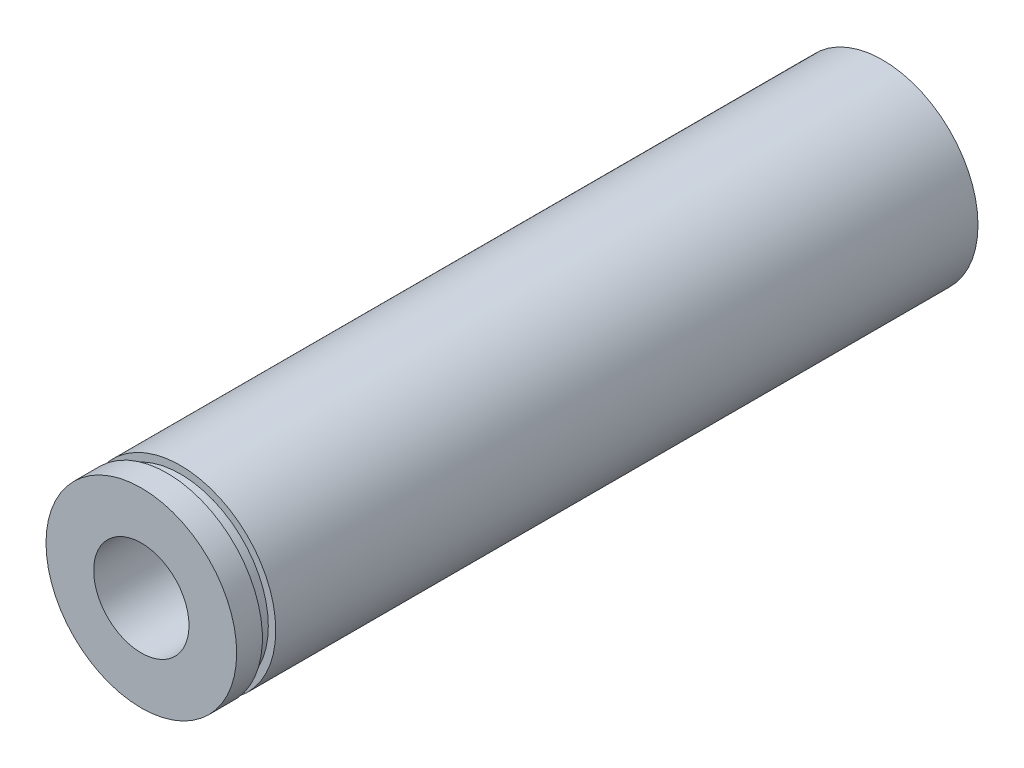
SolidWorks part; units mm, degrees
ref_plane "Front Plane" through (0, 0, 0) normal (0, 0, 1) x (1, 0, 0)
ref_plane "Top Plane" through (0, 0, 0) normal (0, 1, 0) x (1, 0, 0)
ref_plane "Right Plane" through (0, 0, 0) normal (1, 0, 0) x (0, 0, -1)
sketch "Sketch1" plane through (0, 0, 0) normal (0, 0, 1) x (1, 0, 0)
  circle A0 centre (0, 0) radius 6.35
  circle A1 centre (0, 0) radius 3.175
  dimension "D1" = 12.7
  dimension "D2" = 6.35
extrude "Boss-Extrude1" add sketch "Sketch1" along normal mid plane 49.3776
sketch "Sketch2" plane through (0, 0, 0) normal (1, 0, 0) x (0, 0, -1)
  line L0 (-2.4056, 0) -> (1.6345, 0) construction
  line L1 (-22.9743, 6.858) -> (-22.0853, 6.858)
  line L2 (-22.9743, 6.858) -> (-22.9743, 5.8547)
  line L3 (-22.9743, 5.8547) -> (-22.0853, 5.8547)
  line L4 (-22.0853, 6.858) -> (-22.0853, 5.8547)
  line L5 (-24.6888, 6.35) -> (-24.6888, -6.35) construction
  dimension "D1" = 0.889
  dimension "D2" = 5.8547
  dimension "D3" = 1.7145
revolve "Cut-Revolve1" cut sketch "Sketch2" angle 360 about L0
